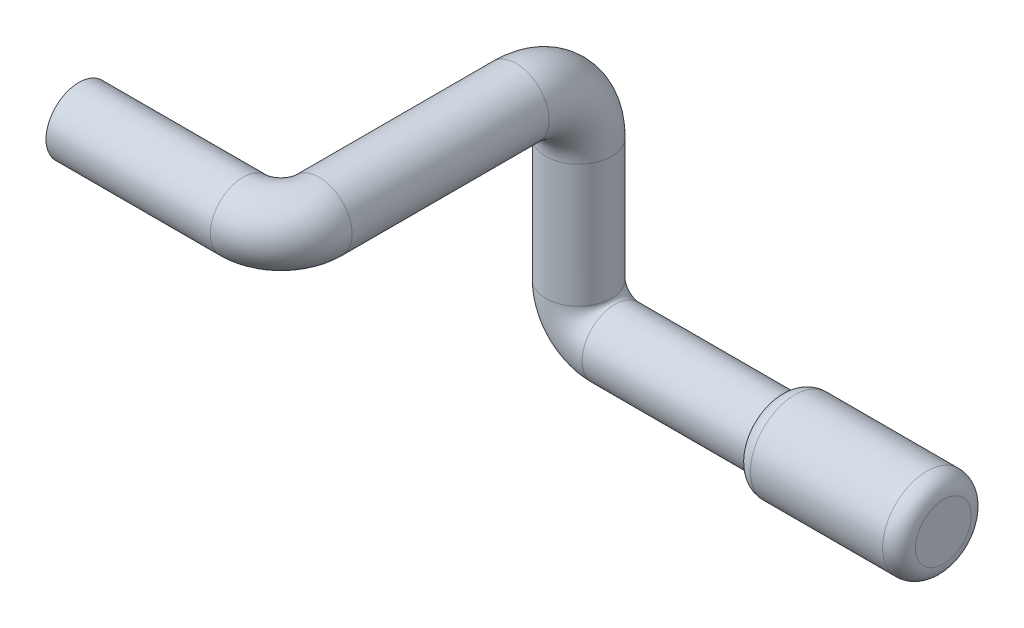
SolidWorks part; units mm, degrees
ref_plane "Front Plane" through (0, 0, 0) normal (0, 0, 1) x (1, 0, 0)
ref_plane "Top Plane" through (0, 0, 0) normal (0, 1, 0) x (1, 0, 0)
ref_plane "Right Plane" through (0, 0, 0) normal (1, 0, 0) x (0, 0, -1)
sketch "Sketch3" plane through (0, 0, 0) normal (0, 1, 0) x (1, 0, 0)
  line L0 (0, 0) -> (25.4, 0)
  arc A0 (25.4, 0) -> (31.2873, 5.8873) centre (25.4, 5.8873) ccw
  dimension "D2" = 5.8873
  dimension "D1" = 25.4
  dimension "D3" = 5.8873
ref_plane "Plane2" through (31.2873, 0, 0) normal (1, 0, 0) x (0, 0, -1)
sketch "Sketch4" plane through (31.2873, 0, 0) normal (1, 0, 0) x (0, 0, -1)
  line L0 (5.8873, 0) -> (36.3673, 0)
  arc A0 (36.3673, 0) -> (46.0364, -9.6691) centre (36.3673, -9.6691) cw
  dimension "D2" = 9.6691
  dimension "D1" = 30.48
  dimension "D3" = 9.6691
ref_plane "Plane3" through (0, 0, -46.0364) normal (0, 0, 1) x (1, 0, 0)
sketch "Sketch5" plane through (0, 0, -46.0364) normal (0, 0, 1) x (1, 0, 0)
  line L0 (31.2873, -9.6691) -> (31.2873, -28.6921)
  line L1 (36.8863, -34.2912) -> (62.2863, -34.2912)
  arc A0 (31.2873, -28.6921) -> (36.8863, -34.2912) centre (36.8863, -28.6921) ccw
  dimension "D1" = 5.5991
  dimension "D2" = 25.4
  dimension "D3" = 19.023
sketch "Sketch6" plane through (0, 0, 0) normal (1, 0, 0) x (0, 0, -1)
  circle A0 centre (0, 0) radius 5.08
  dimension "D1" = 10.16
curve "CompCurve1"
sweep "Sweep1" add profiles "Sketch6" path "CompCurve1"
sketch "Sketch7" plane through (62.2863, 0, 0) normal (1, 0, 0) x (0, 0, -1)
  circle A0 centre (46.0364, -34.2912) radius 6.858
  dimension "D1" = 13.716
extrude "Boss-Extrude1" add sketch "Sketch7" along normal blind 25.4
fillet "Fillet1" radius 2.54 2 edges at (87.6863, -27.4332, -46.0364) (62.2863, -27.4332, -46.0364)
